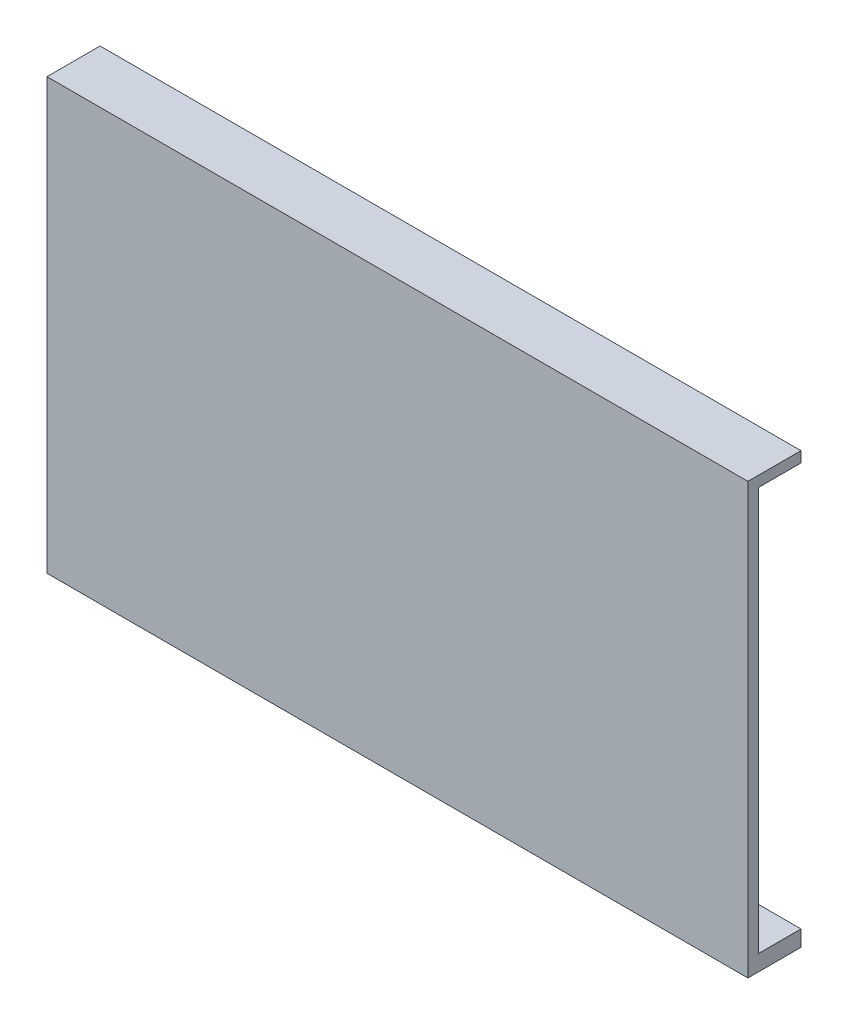
SolidWorks part; units mm, degrees
ref_plane "Alzado" through (0, 0, 0) normal (0, 0, 1) x (1, 0, 0)
ref_plane "Planta" through (0, 0, 0) normal (0, 1, 0) x (1, 0, 0)
ref_plane "Vista lateral" through (0, 0, 0) normal (1, 0, 0) x (0, 0, -1)
sketch "Croquis1" plane through (0, 0, 0) normal (0, 0, 1) x (1, 0, 0)
  line L1 (-66, 81) -> (66, 81)
  line L2 (-66, 81) -> (-66, 0)
  line L3 (-66, 0) -> (66, 0)
  line L4 (66, 81) -> (66, 0)
  dimension "D1" = 132
  dimension "D2" = 81
extrude "Saliente-Extruir1" add sketch "Croquis1" along normal blind 10
sketch "Croquis2" plane through (0, 0, 0) normal (0, 0, -1) x (-1, 0, 0)
  line L0 (-66, 0) -> (-66, 81) construction
  line L1 (-66, 79) -> (66, 79)
  line L2 (-66, 79) -> (-66, 3)
  line L3 (-66, 3) -> (66, 3)
  line L4 (66, 79) -> (66, 3)
  line L6 (-66, 81) -> (66, 81) construction
  line L8 (66, 81) -> (66, 0) construction
  line L9 (66, 0) -> (-66, 0) construction
  dimension "D1" = 3
  dimension "D4" = 2
extrude "Cortar-Extruir1" cut sketch "Croquis2" against normal blind 8
